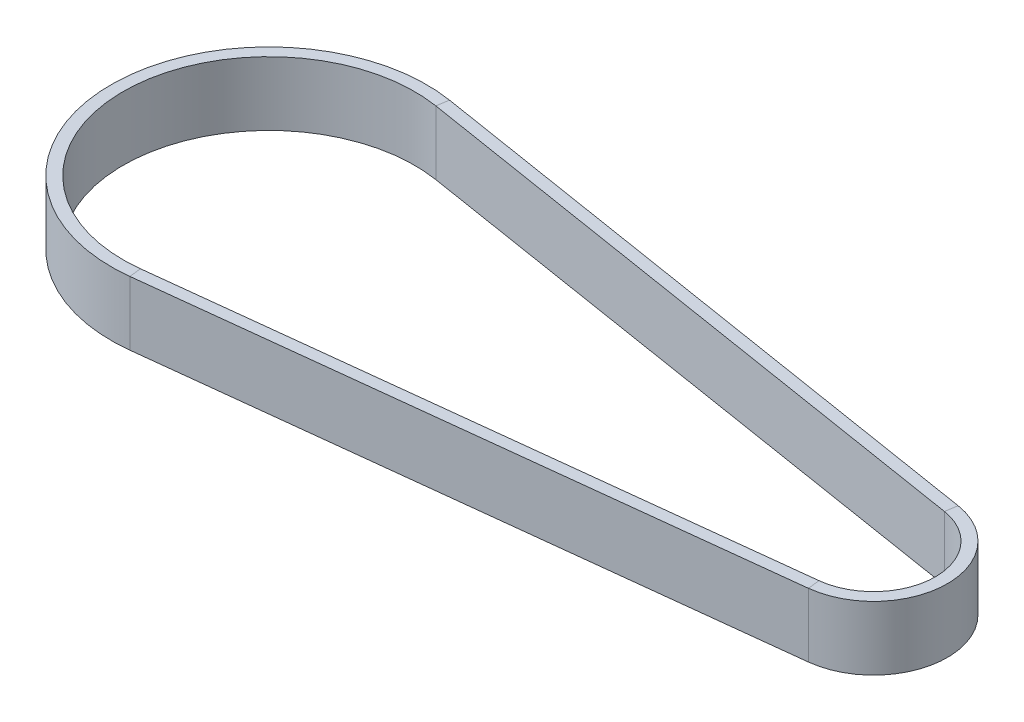
SolidWorks part; units mm, degrees
ref_plane "Front Plane" through (0, 0, 0) normal (0, 0, 1) x (1, 0, 0)
ref_plane "Top Plane" through (0, 0, 0) normal (0, 1, 0) x (1, 0, 0)
ref_plane "Right Plane" through (0, 0, 0) normal (1, 0, 0) x (0, 0, -1)
ref_axis "X" through (-88.99, 0, 0) along (1, 0, 0)
ref_axis "Y" through (0, 0, -88.99) along (0, 0, 1)
ref_axis "Z" through (0, 55, 0) along (0, -1, 0)
sketch "Sketch1" plane through (0, 0, 0) normal (0, 1, 0) x (1, 0, 0)
  line L0 (245.7589, 4211.4599) -> (397.3985, 4187.1819)
  line L1 (396.6287, 4153.5042) -> (244.0382, 4136.1803)
  arc A0 (245.7589, 4211.4599) -> (244.0382, 4136.1803) centre (239.7515, 4173.9377) ccw
  arc A1 (396.6287, 4153.5042) -> (397.3985, 4187.1819) centre (394.711, 4170.3957) ccw
  point P13 (394.711, 4170.3957)
  dimension "D1" = 17
  dimension "D2" = 38
ref_plane "Plane1" through (244.0382, 0, -4136.1803) normal (-0.9936, 0, 0.1128) x (0.1128, 0, 0.9936)
sketch "Sketch2" plane through (244.0382, 0, -4136.1803) normal (-0.9936, 0, 0.1128) x (0.1128, 0, 0.9936)
  line L0 (0, 0) -> (-33.3759, 0) construction
  line L1 (-1.5, 8) -> (1.5, 8)
  line L2 (-1.5, 8) -> (-1.5, -8)
  line L3 (-1.5, -8) -> (1.5, -8)
  line L4 (1.5, 8) -> (1.5, -8)
  line L5 (-1.5, 8) -> (1.5, -8) construction
  line L6 (-1.5, -8) -> (1.5, 8) construction
  point P0 (0, 0)
  dimension "D1" = 3
  dimension "D2" = 16
sweep "Sweep1" add profiles "Sketch2" path "Sketch1"
